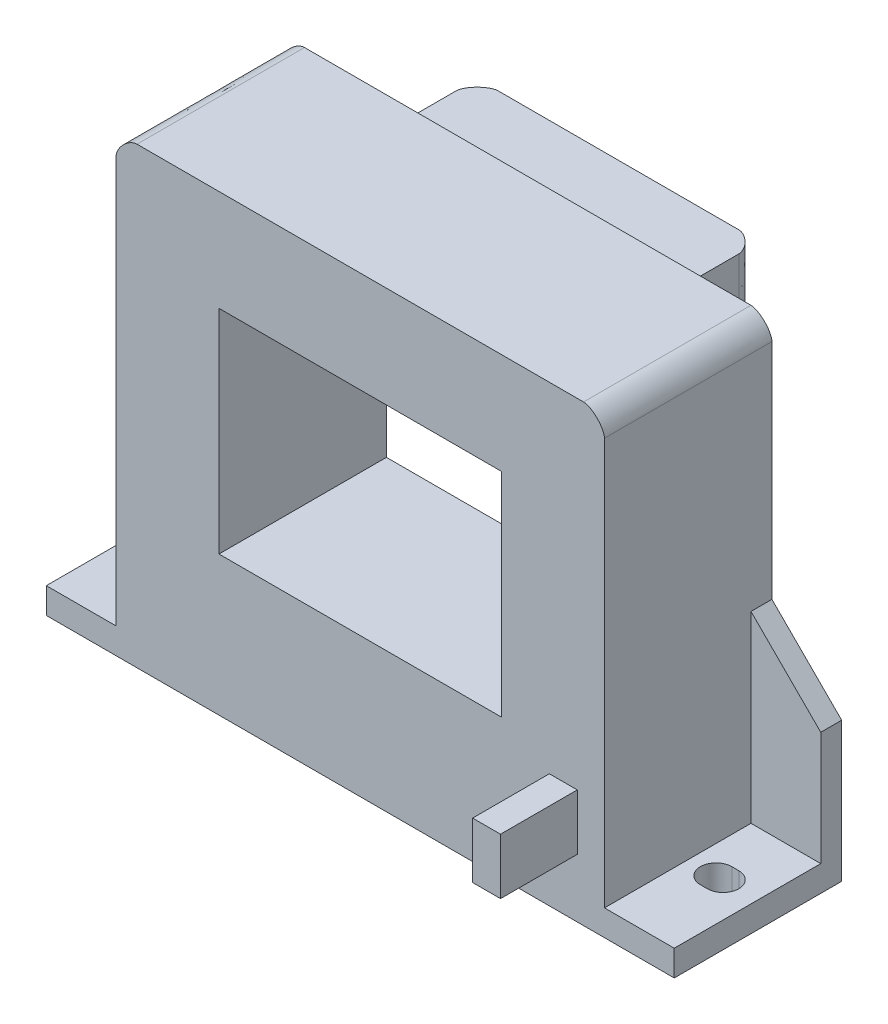
SolidWorks part; units mm, degrees
ref_plane "Front Plane" through (0, 0, 0) normal (0, 0, 1) x (1, 0, 0)
ref_plane "Top Plane" through (0, 0, 0) normal (0, 1, 0) x (1, 0, 0)
ref_plane "Right Plane" through (0, 0, 0) normal (1, 0, 0) x (0, 0, -1)
sketch "Sketch1" plane through (0, 0, 0) normal (0, 0, 1) x (1, 0, 0)
  line L1 (-35, 0) -> (35, 0)
  line L2 (-35, 0) -> (-35, 65)
  line L3 (-35, 65) -> (35, 65)
  line L4 (35, 0) -> (35, 65)
  point P4 (0, 0)
  dimension "D1" = 70
  dimension "D2" = 65
extrude "Boss-Extrude1" add sketch "Sketch1" along normal mid plane 24
sketch "Sketch2" plane through (35, 0, 0) normal (1, 0, 0) x (0, 0, -1)
  line L0 (12, 20) -> (12, 0)
  line L1 (12, 0) -> (12, 65) construction
  line L2 (12, 0) -> (-12, 0)
  line L3 (-12, 0) -> (-12, 3.7)
  line L4 (-12, 0) -> (-12, 65) construction
  line L5 (-12, 3.7) -> (9, 3.7)
  line L6 (9, 3.7) -> (9, 20)
  line L7 (9, 20) -> (12, 20)
  dimension "D1" = 3
  dimension "D2" = 3.7
  dimension "D3" = 20
extrude "Boss-Extrude2" add sketch "Sketch2" against normal blind 90 from offset 10
sketch "Sketch3" plane through (0, 0, -12) normal (0, 0, -1) x (-1, 0, 0)
  line L0 (-45, 20) -> (-35, 20)
  line L1 (-35, 20) -> (-35, 30)
  line L2 (-35, 20) -> (-35, 65) construction
  line L3 (-35, 30) -> (-45, 20)
  line L4 (0, -18.5477) -> (0, 72.3694) construction
  line L5 (35, 30) -> (45, 20)
  line L6 (35, 20) -> (35, 30)
  line L7 (45, 20) -> (35, 20)
  dimension "D1" = 45
extrude "Boss-Extrude3" add sketch "Sketch3" against normal up to surface (3 mm away) up to face at (40, 11.85, -9)
sketch "Sketch4" plane through (0, 0, -12) normal (0, 0, 1) x (1, 0, 0)
  line L0 (35, 65) -> (-35, 65) construction
  line L1 (-20.25, 60.5) -> (20.25, 60.5)
  line L2 (-20.25, 60.5) -> (-20.25, 50.5)
  line L3 (-20.25, 50.5) -> (20.25, 50.5)
  line L4 (20.25, 60.5) -> (20.25, 50.5)
  point P4 (0, 60.5)
  point P7 (0, 65)
  dimension "D1" = 10
  dimension "D2" = 40.5
  dimension "D3" = 4.5
extrude "Boss-Extrude4" add sketch "Sketch4" against normal blind 13
sketch "Sketch5" plane through (0, 0, 12) normal (0, 0, 1) x (1, 0, 0)
  line L0 (35, 65) -> (-35, 65) construction
  line L1 (-20.25, 50.5) -> (20.25, 50.5)
  line L2 (-20.25, 50.5) -> (-20.25, 20)
  line L3 (-20.25, 20) -> (20.25, 20)
  line L4 (20.25, 50.5) -> (20.25, 20)
  line L5 (-45, 0) -> (45, 0) construction
  point P4 (0, 65)
  point P7 (0, 20)
  dimension "D1" = 40.5
  dimension "D2" = 30.5
  dimension "D3" = 20
extrude "Cut-Extrude1" cut sketch "Sketch5" against normal up to surface (24 mm away) up to face at (0, 55.5, -12)
sketch "Sketch6" plane through (0, 0, 12) normal (0, 0, 1) x (1, 0, 0)
  line L0 (45, 3.7) -> (45, 0) construction
  line L1 (27.1, 16.4) -> (31.1, 16.4)
  line L2 (27.1, 16.4) -> (27.1, 8.4)
  line L3 (27.1, 8.4) -> (31.1, 8.4)
  line L4 (31.1, 16.4) -> (31.1, 8.4)
  line L5 (-45, 0) -> (45, 0) construction
  dimension "D1" = 13.9
  dimension "D2" = 8.4
  dimension "D3" = 4
  dimension "D4" = 8
extrude "Boss-Extrude5" add sketch "Sketch6" along normal blind 11
fillet "Fillet1" radius 3 4 edges at (-35, 65, 0) (35, 65, 0) (-20.25, 55.5, -25) (20.25, 55.5, -25) conic rho 0.3
sketch "Sketch7" plane through (0, 3.7, 0) normal (0, 1, 0) x (1, 0, 0)
  line L0 (-45, 12) -> (-35, 12) construction
  line L1 (0, -35.4979) -> (0, 46.7397) construction
  line L2 (39, 2.25) -> (40, 2.25)
  line L3 (39, -2.25) -> (40, -2.25)
  circle A0 centre (-39, 0) radius 2.25
  arc A1 (39, -2.25) -> (39, 2.25) centre (39, 0) cw
  arc A2 (40, 2.25) -> (40, -2.25) centre (40, 0) cw
  dimension "D3" = 4.5
  dimension "D1" = 39
  dimension "D2" = 12
  dimension "D4" = 1
extrude "Cut-Extrude2" cut sketch "Sketch7" against normal up to surface (3.7 mm away) up to face at (0, 0, 0)
